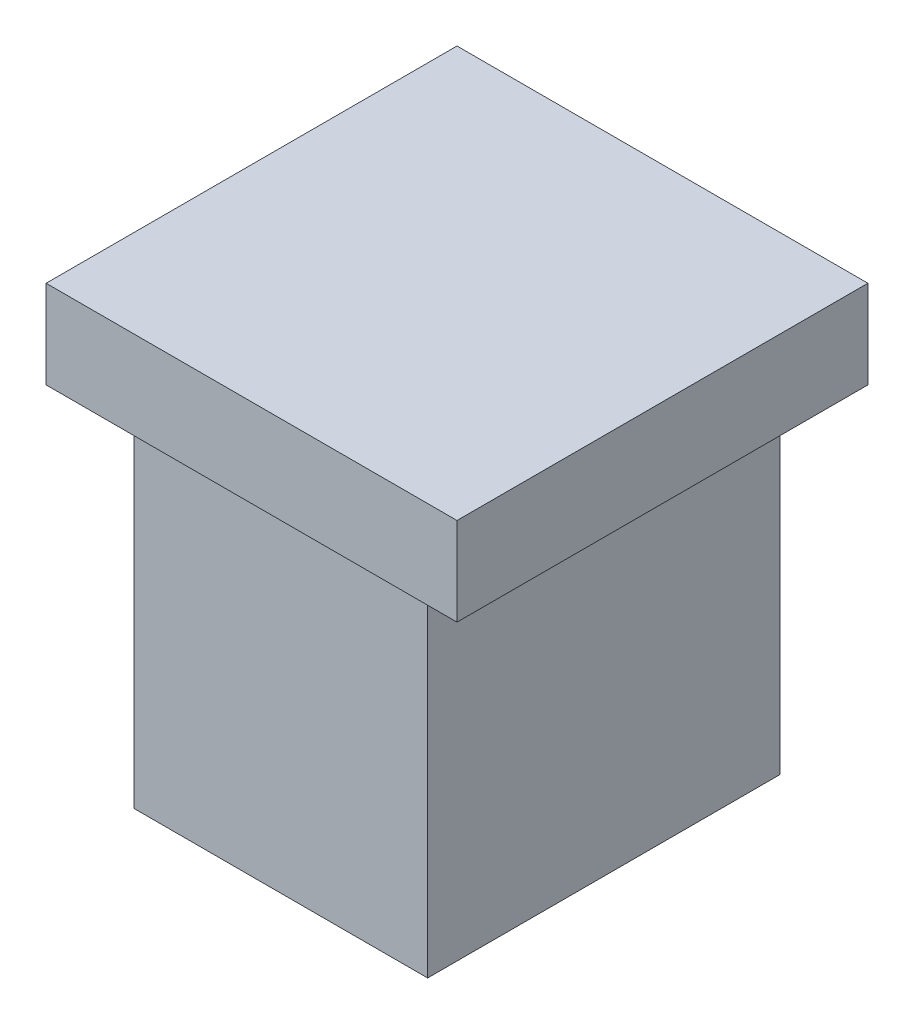
SolidWorks part; units mm, degrees
ref_plane "Спереди" through (0, 0, 0) normal (0, 0, 1) x (1, 0, 0)
ref_plane "Сверху" through (0, 0, 0) normal (0, 1, 0) x (1, 0, 0)
ref_plane "Справа" through (0, 0, 0) normal (1, 0, 0) x (0, 0, -1)
sketch "Эскиз1" plane through (0, 0, 0) normal (0, 1, 0) x (1, 0, 0)
  line L1 (5, 6) -> (-5, 6)
  line L2 (5, 6) -> (5, -6)
  line L3 (5, -6) -> (-5, -6)
  line L4 (-5, 6) -> (-5, -6)
  line L5 (5, 6) -> (-5, -6) construction
  line L6 (5, -6) -> (-5, 6) construction
  line L7 (7, 7) -> (-7, 7)
  line L8 (7, 7) -> (7, -7)
  line L9 (7, -7) -> (-7, -7)
  line L10 (-7, 7) -> (-7, -7)
  line L11 (7, 7) -> (-7, -7) construction
  line L12 (7, -7) -> (-7, 7) construction
  point P0 (0, 0)
  point P6 (0, 0)
  dimension "D1" = 10
  dimension "D2" = 12
  dimension "D3" = 14
extrude "Бобышка-Вытянуть1" add sketch "Эскиз1" along normal blind 12 contours L2 L1 L4 L3
extrude "Бобышка-Вытянуть2" add sketch "Эскиз1<3>" along normal blind 3 from surface contours L1 L4 L3 L2 | L7 L10 L9 L8 L4 L1 L2 L3 region at (0, 0, 0) region at (6.802, 0, 0) starting at face at (0, 12, 0)
sketch "Эскиз1<3>" plane through (0, 0, 0) normal (0, 1, 0) x (1, 0, 0) same geometry as "Эскиз1"
